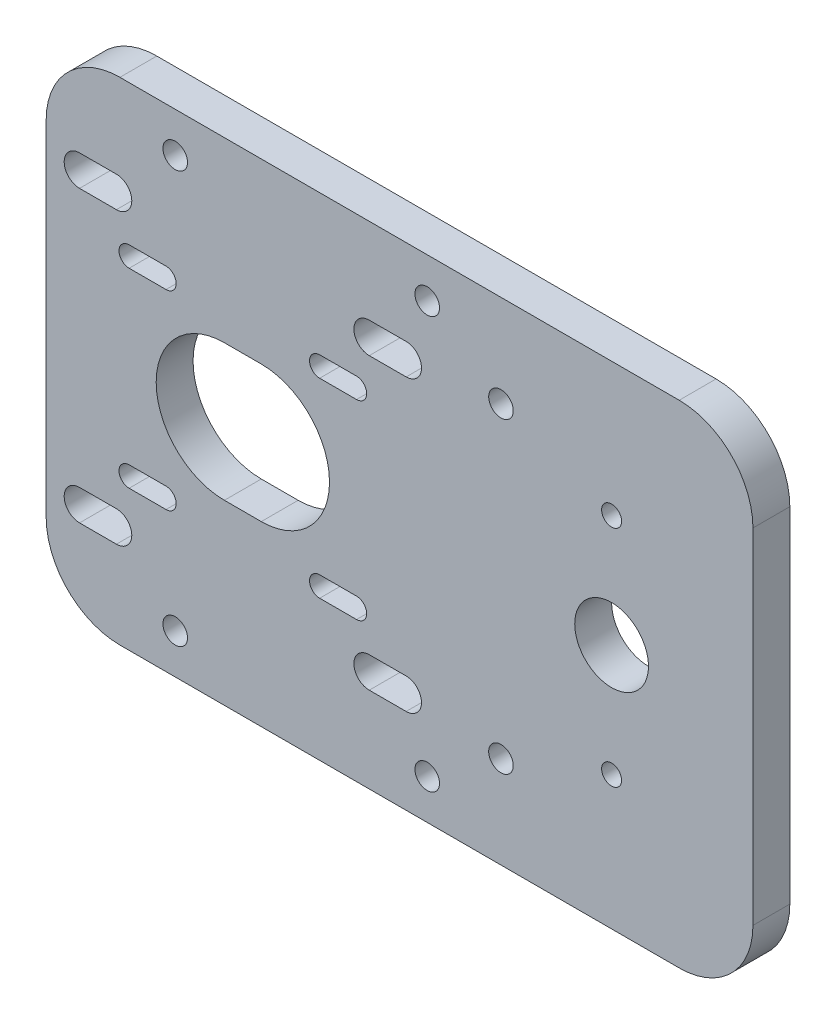
SolidWorks part; units mm, degrees
ref_plane "Alzado" through (0, 0, 0) normal (0, 0, 1) x (1, 0, 0)
ref_plane "Planta" through (0, 0, 0) normal (0, 1, 0) x (1, 0, 0)
ref_plane "Vista lateral" through (0, 0, 0) normal (1, 0, 0) x (0, 0, -1)
sketch "Croquis1" plane through (0, 0, 0) normal (0, 0, 1) x (1, 0, 0)
  line L1 (0, 0) -> (115, 0)
  line L2 (0, 0) -> (0, 80)
  line L3 (0, 80) -> (115, 80)
  line L4 (115, 0) -> (115, 80)
  dimension "D1" = 80
  dimension "D2" = 115
extrude "Saliente-Extruir1" add sketch "Croquis1" along normal blind 6
sketch "Croquis2" plane through (0, 0, 0) normal (0, 0, -1) x (-1, 0, 0)
  line L0 (0, 80) -> (0, 0) construction
  line L1 (0, 40) -> (-115, 40) construction
  line L4 (-115, 0) -> (-115, 80) construction
  line L7 (-29, 40) -> (-35, 40) construction
  line L10 (-29, 28.9) -> (-35, 28.9)
  line L19 (-29, 51.1) -> (-35, 51.1)
  line L20 (-13.5, 24.5) -> (-19.5, 24.5) construction
  line L21 (-13.5, 22.85) -> (-19.5, 22.85)
  line L22 (-13.5, 26.15) -> (-19.5, 26.15)
  line L23 (-44.5, 55.5) -> (-50.5, 55.5) construction
  line L24 (-44.5, 53.85) -> (-50.5, 53.85)
  line L25 (-44.5, 57.15) -> (-50.5, 57.15)
  line L26 (-44.5, 24.5) -> (-50.5, 24.5) construction
  line L27 (-44.5, 22.85) -> (-50.5, 22.85)
  line L28 (-44.5, 26.15) -> (-50.5, 26.15)
  line L29 (-13.5, 55.5) -> (-19.5, 55.5) construction
  line L30 (-13.5, 53.85) -> (-19.5, 53.85)
  line L31 (-13.5, 57.15) -> (-19.5, 57.15)
  line L32 (-92, 0) -> (-92, 80) construction
  line L33 (0, 0) -> (-115, 0) construction
  line L34 (-115, 80) -> (0, 80) construction
  line L35 (-61, 0) -> (-61, 80) construction
  line L36 (-52.57, 16.43) -> (-58.57, 16.43) construction
  line L37 (-52.57, 13.93) -> (-58.57, 13.93)
  line L38 (-52.57, 18.93) -> (-58.57, 18.93)
  line L39 (-5.43, 16.43) -> (-11.43, 16.43) construction
  line L40 (-5.43, 13.93) -> (-11.43, 13.93)
  line L41 (-5.43, 18.93) -> (-11.43, 18.93)
  line L42 (-52.57, 63.57) -> (-58.57, 63.57) construction
  line L43 (-52.57, 61.07) -> (-58.57, 61.07)
  line L44 (-52.57, 66.07) -> (-58.57, 66.07)
  line L45 (-5.43, 63.57) -> (-11.43, 63.57) construction
  line L46 (-5.43, 61.07) -> (-11.43, 61.07)
  line L47 (-5.43, 66.07) -> (-11.43, 66.07)
  circle A5 centre (-92, 40) radius 6
  circle A15 centre (-92, 21.75) radius 1.625
  circle A16 centre (-92, 58.25) radius 1.625
  arc A19 (-29, 28.9) -> (-29, 51.1) centre (-29, 40) ccw
  arc A20 (-35, 51.1) -> (-35, 28.9) centre (-35, 40) ccw
  arc A21 (-13.5, 22.85) -> (-13.5, 26.15) centre (-13.5, 24.5) ccw
  arc A22 (-19.5, 26.15) -> (-19.5, 22.85) centre (-19.5, 24.5) ccw
  arc A23 (-44.5, 53.85) -> (-44.5, 57.15) centre (-44.5, 55.5) ccw
  arc A24 (-50.5, 57.15) -> (-50.5, 53.85) centre (-50.5, 55.5) ccw
  arc A25 (-44.5, 22.85) -> (-44.5, 26.15) centre (-44.5, 24.5) ccw
  arc A26 (-50.5, 26.15) -> (-50.5, 22.85) centre (-50.5, 24.5) ccw
  arc A27 (-13.5, 53.85) -> (-13.5, 57.15) centre (-13.5, 55.5) ccw
  arc A28 (-19.5, 57.15) -> (-19.5, 53.85) centre (-19.5, 55.5) ccw
  arc A29 (-52.57, 13.93) -> (-52.57, 18.93) centre (-52.57, 16.43) ccw
  arc A30 (-58.57, 18.93) -> (-58.57, 13.93) centre (-58.57, 16.43) ccw
  arc A31 (-5.43, 13.93) -> (-5.43, 18.93) centre (-5.43, 16.43) ccw
  arc A32 (-11.43, 18.93) -> (-11.43, 13.93) centre (-11.43, 16.43) ccw
  arc A33 (-52.57, 61.07) -> (-52.57, 66.07) centre (-52.57, 63.57) ccw
  arc A34 (-58.57, 66.07) -> (-58.57, 61.07) centre (-58.57, 63.57) ccw
  arc A35 (-5.43, 61.07) -> (-5.43, 66.07) centre (-5.43, 63.57) ccw
  arc A36 (-11.43, 66.07) -> (-11.43, 61.07) centre (-11.43, 63.57) ccw
  circle A37 centre (-74, 15) radius 2
  circle A38 centre (-74, 65) radius 2
  point P6 (-32, 40)
  point P19 (-16.5, 24.5)
  point P28 (-47.5, 55.5)
  point P35 (-47.5, 24.5)
  point P41 (-55.57, 16.43)
  point P48 (-16.5, 55.5)
  point P63 (-8.43, 16.43)
  point P72 (-55.57, 63.57)
  point P79 (-8.43, 63.57)
  dimension "D2" = 6
  dimension "D3" = 11.1
  dimension "D4" = 3.3
  dimension "D5" = 6
  dimension "D6" = 12
  dimension "D13" = 3.25
  dimension "D14" = 3.25
  dimension "D29" = 2.5
  dimension "D32" = 2.5
  dimension "D34" = 2.5
  dimension "D36" = 2.5
  dimension "D45" = 4
  dimension "D46" = 4
  dimension "D7" = 15.5
  dimension "D8" = 15.5
  dimension "D9" = 3.3
  dimension "D10" = 6
  dimension "D11" = 23
  dimension "D12" = 40
  dimension "D15" = 18.25
  dimension "D16" = 18.25
  dimension "D17" = 3.3
  dimension "D18" = 6
  dimension "D19" = 3.3
  dimension "D20" = 6
  dimension "D21" = 15.5
  dimension "D22" = 15.5
  dimension "D23" = 15.5
  dimension "D24" = 15.5
  dimension "D25" = 15.5
  dimension "D26" = 15.5
  dimension "D27" = 60
  dimension "D28" = 26
  dimension "D30" = 6
  dimension "D31" = 6
  dimension "D33" = 6
  dimension "D35" = 6
  dimension "D37" = 23.57
  dimension "D38" = 23.57
  dimension "D39" = 23.57
  dimension "D40" = 23.57
  dimension "D41" = 23.57
  dimension "D42" = 23.57
  dimension "D43" = 23.57
  dimension "D44" = 23.57
  dimension "D47" = 15
  dimension "D48" = 41
  dimension "D49" = 41
  dimension "D50" = 15
extrude "Cortar-Extruir1" cut sketch "Croquis2" against normal through all
fillet "Redondeo1" radius 12 4 edges at (115, 0, 3) (115, 80, 3) (0, 0, 3) (0, 80, 3)
sketch "Croquis3" plane through (0, 0, 0) normal (0, 0, -1) x (-1, 0, 0)
  line L0 (-12, 0) -> (-103, 0) construction
  line L1 (0, 68) -> (0, 12) construction
  line L2 (-103, 80) -> (-12, 80) construction
  circle A0 centre (-21, 6.5) radius 2
  circle A1 centre (-62, 6.5) radius 2
  circle A2 centre (-62, 73.5) radius 2
  circle A3 centre (-21, 73.5) radius 2
  dimension "D1" = 4
  dimension "D2" = 4
  dimension "D3" = 4
  dimension "D4" = 4
  dimension "D5" = 6.5
  dimension "D6" = 6.5
  dimension "D7" = 21
  dimension "D8" = 62
  dimension "D9" = 6.5
  dimension "D10" = 6.5
  dimension "D11" = 21
  dimension "D12" = 62
extrude "Cortar-Extruir2" cut sketch "Croquis3" against normal through all
